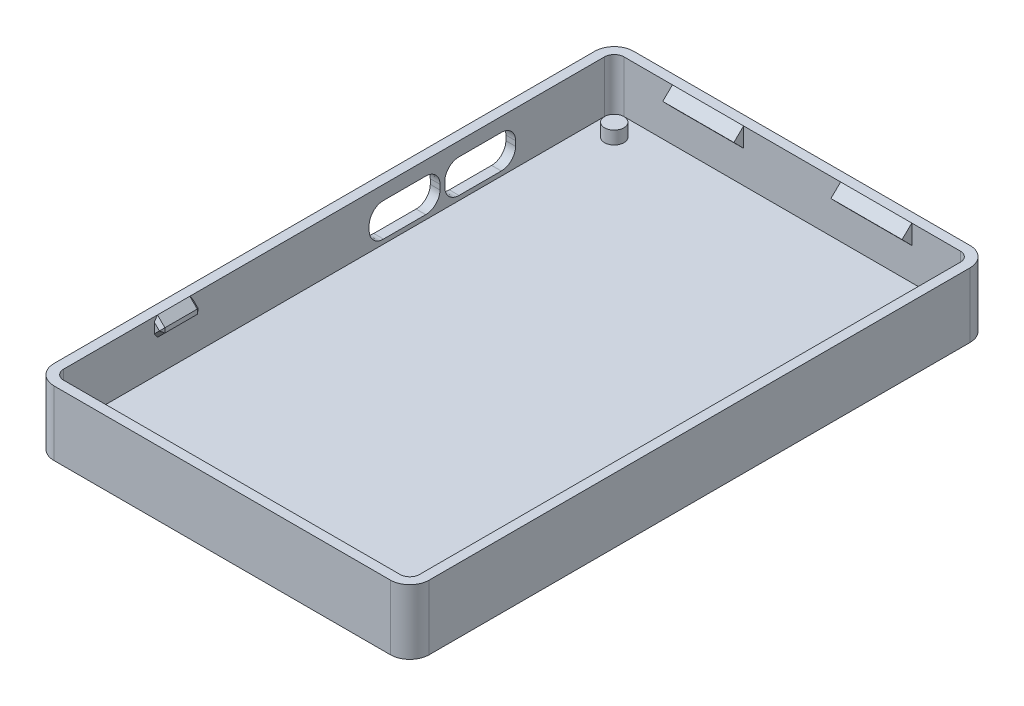
SolidWorks part; units mm, degrees
ref_plane "前视基准面" through (0, 0, 0) normal (0, 0, 1) x (1, 0, 0)
ref_plane "上视基准面" through (0, 0, 0) normal (0, 1, 0) x (1, 0, 0)
ref_plane "右视基准面" through (0, 0, 0) normal (1, 0, 0) x (0, 0, -1)
other "Configuration Table"
sketch "草图1" plane through (0, 0, 0) normal (0, 1, 0) x (1, 0, 0)
  line L1 (3, 0) -> (55, 0)
  line L2 (0, 3) -> (0, 86.6)
  line L3 (3, 89.6) -> (55, 89.6)
  line L4 (58, 3) -> (58, 86.6)
  arc A0 (58, 86.6) -> (55, 89.6) centre (55, 86.6) ccw
  arc A1 (55, 0) -> (58, 3) centre (55, 3) ccw
  arc A2 (3, 0) -> (0, 3) centre (3, 3) cw
  arc A3 (0, 86.6) -> (3, 89.6) centre (3, 86.6) cw
  point P7 (58, 89.6)
  point P10 (58, 0)
  point P13 (0, 0)
  point P16 (0, 89.6)
  dimension "D3" = 3
  dimension "D1" = 89.6
  dimension "D2" = 58
extrude "凸台-拉伸1" add sketch "草图1" along normal blind 2
sketch "草图3" plane through (0, 2, 0) normal (0, 1, 0) x (1, 0, 0)
  line L0 (0, 86.6) -> (0, 3) construction
  line L1 (3, 0) -> (55, 0) construction
  line L2 (58, 3) -> (58, 86.6) construction
  line L3 (55, 89.6) -> (3, 89.6) construction
  line L4 (0, 86.6) -> (0, 3)
  line L5 (3, 0) -> (55, 0)
  line L6 (58, 3) -> (58, 86.6)
  line L7 (55, 89.6) -> (3, 89.6)
  line L8 (1.5, 86.6) -> (1.5, 3)
  line L9 (3, 1.5) -> (55, 1.5)
  line L10 (56.5, 3) -> (56.5, 86.6)
  line L11 (55, 88.1) -> (3, 88.1)
  arc A0 (0, 3) -> (3, 0) centre (3, 3) ccw construction
  arc A1 (55, 0) -> (58, 3) centre (55, 3) ccw construction
  arc A2 (58, 86.6) -> (55, 89.6) centre (55, 86.6) ccw construction
  arc A3 (3, 89.6) -> (0, 86.6) centre (3, 86.6) ccw construction
  arc A4 (0, 3) -> (3, 0) centre (3, 3) ccw
  arc A5 (55, 0) -> (58, 3) centre (55, 3) ccw
  arc A6 (58, 86.6) -> (55, 89.6) centre (55, 86.6) ccw
  arc A7 (3, 89.6) -> (0, 86.6) centre (3, 86.6) ccw
  arc A8 (1.5, 3) -> (3, 1.5) centre (3, 3) ccw
  arc A9 (55, 1.5) -> (56.5, 3) centre (55, 3) ccw
  arc A10 (56.5, 86.6) -> (55, 88.1) centre (55, 86.6) ccw
  arc A11 (3, 88.1) -> (1.5, 86.6) centre (3, 86.6) ccw
  dimension "D1" = 1.5
extrude "凸台-拉伸2" add sketch "草图3" along normal blind 11
sketch "草图5" plane through (0, 2, 0) normal (0, 1, 0) x (1, 0, 0)
  line L0 (55, 88.1) -> (3, 88.1) construction
  line L1 (1.5, 86.6) -> (1.5, 3) construction
  line L2 (29, 89.6) -> (29, 0) construction
  line L3 (55, 89.6) -> (3, 89.6) construction
  line L4 (3, 0) -> (55, 0) construction
  line L5 (0, 44.8) -> (58, 44.8) construction
  line L6 (0, 86.6) -> (0, 3) construction
  line L7 (58, 3) -> (58, 86.6) construction
  circle A0 centre (5, 84.6) radius 1.5
  circle A1 centre (53, 84.6) radius 1.5
  circle A2 centre (53, 5) radius 1.5
  circle A3 centre (5, 5) radius 1.5
  dimension "D3" = 3
  dimension "D1" = 3.5
  dimension "D2" = 3.5
extrude "凸台-拉伸3" add sketch "草图5" along normal blind 2
extrude "切除-拉伸1" cut sketch "草图6" against normal blind 2 contours S23 L27 S22 L26 S21 L25 S20 L24 L6 S7 L7 S5 L4 S4 L5 S6 | S7 L6 S6 L5 S4 L4 S5 L7 | S31 L31 S30 L30 S29 L29 S28 L28 L23 S15 L20 S12 L21 S13 L22 S14 | S15 L23 S14 L22 S13 L21 S12 L20 region at (0, 5.27, -67.3785) region at (0, 5.27, -55.6945) region at (0, 7.7291, -67.3785) region at (0, 7.7291, -55.6945)
sketch "草图6" plane through (0, 2, -82.9995) normal (-1, 0, 0) x (0, 1, 0)
  line L4 (3.65, -20.091) -> (2.89, -20.091)
  line L5 (1.69, -18.891) -> (1.69, -12.351)
  line L6 (2.89, -11.151) -> (3.65, -11.151)
  line L7 (4.85, -12.351) -> (4.85, -18.891)
  line L16 (-2, 3.6005) -> (-2, -79.9995)
  line L17 (-2, -79.9995) -> (8, -79.9995)
  line L19 (8, 3.6005) -> (-2, 3.6005)
  line L20 (4.85, -24.0351) -> (4.85, -30.5751)
  line L21 (3.65, -31.7751) -> (2.89, -31.7751)
  line L22 (1.69, -30.5751) -> (1.69, -24.0351)
  line L23 (2.89, -22.8351) -> (3.65, -22.8351)
  line L24 (5.85, -12.351) -> (5.85, -18.891)
  line L25 (3.65, -21.091) -> (2.89, -21.091)
  line L26 (0.69, -18.891) -> (0.69, -12.351)
  line L27 (2.89, -10.151) -> (3.65, -10.151)
  line L28 (5.85, -24.0351) -> (5.85, -30.5751)
  line L29 (3.65, -32.7751) -> (2.89, -32.7751)
  line L30 (0.69, -30.5751) -> (0.69, -24.0351)
  line L31 (2.89, -21.8351) -> (3.65, -21.8351)
  line L36 (8, -79.9995) -> (8, 3.6005)
  spline S4 degree 3 poles (2.89, -20.091) (2.1871, -20.091) (1.69, -19.594) (1.69, -18.891) knots 0 0 0 0 1 1 1 1 weights 1 0.804738 0.804738 1
  spline S5 degree 3 poles (4.85, -18.891) (4.85, -19.594) (4.353, -20.091) (3.65, -20.091) knots 0 0 0 0 1 1 1 1 weights 1 0.804738 0.804738 1
  spline S6 degree 3 poles (1.69, -12.351) (1.69, -11.6481) (2.1871, -11.151) (2.89, -11.151) knots 0 0 0 0 1 1 1 1 weights 1 0.804738 0.804738 1
  spline S7 degree 3 poles (3.65, -11.151) (4.353, -11.151) (4.85, -11.6481) (4.85, -12.351) knots 0 0 0 0 1 1 1 1 weights 1 0.804738 0.804738 1
  spline S12 degree 3 poles (4.85, -30.5751) (4.85, -31.278) (4.353, -31.7751) (3.65, -31.7751) knots 0 0 0 0 1 1 1 1 weights 1 0.804738 0.804738 1
  spline S13 degree 3 poles (2.89, -31.7751) (2.1871, -31.7751) (1.69, -31.278) (1.69, -30.5751) knots 0 0 0 0 1 1 1 1 weights 1 0.804738 0.804738 1
  spline S14 degree 3 poles (1.69, -24.0351) (1.69, -23.3321) (2.1871, -22.8351) (2.89, -22.8351) knots 0 0 0 0 1 1 1 1 weights 1 0.804738 0.804738 1
  spline S15 degree 3 poles (3.65, -22.8351) (4.353, -22.8351) (4.85, -23.3321) (4.85, -24.0351) knots 0 0 0 0 1 1 1 1 weights 1 0.804738 0.804738 1
  spline S20 degree 3 poles (5.85, -18.891) (5.85, -19.1658) (5.7555, -19.7032) (5.2541, -20.4951) (4.4622, -20.9965) (3.9248, -21.091) (3.65, -21.091) knots 0 0 0 0 0.25 0.5 0.75 1 1 1 1
  spline S21 degree 3 poles (2.89, -21.091) (2.6152, -21.091) (2.0779, -20.9965) (1.286, -20.4951) (0.7845, -19.7032) (0.69, -19.1658) (0.69, -18.891) knots 0 0 0 0 0.25 0.5 0.75 1 1 1 1
  spline S22 degree 3 poles (0.69, -12.351) (0.69, -12.0762) (0.7845, -11.5389) (1.286, -10.747) (2.0779, -10.2456) (2.6152, -10.151) (2.89, -10.151) knots 0 0 0 0 0.25 0.5 0.75 1 1 1 1
  spline S23 degree 3 poles (3.65, -10.151) (3.9248, -10.151) (4.4622, -10.2456) (5.2541, -10.747) (5.7555, -11.5389) (5.85, -12.0762) (5.85, -12.351) knots 0 0 0 0 0.25 0.5 0.75 1 1 1 1
  spline S28 degree 3 poles (5.85, -30.5751) (5.85, -30.8499) (5.7555, -31.3872) (5.2541, -32.1791) (4.4622, -32.6805) (3.9248, -32.7751) (3.65, -32.7751) knots 0 0 0 0 0.25 0.5 0.75 1 1 1 1
  spline S29 degree 3 poles (2.89, -32.7751) (2.6152, -32.7751) (2.0779, -32.6805) (1.286, -32.1791) (0.7845, -31.3872) (0.69, -30.8499) (0.69, -30.5751) knots 0 0 0 0 0.25 0.5 0.75 1 1 1 1
  spline S30 degree 3 poles (0.69, -24.0351) (0.69, -23.7603) (0.7845, -23.2229) (1.286, -22.431) (2.0779, -21.9296) (2.6152, -21.8351) (2.89, -21.8351) knots 0 0 0 0 0.25 0.5 0.75 1 1 1 1
  spline S31 degree 3 poles (3.65, -21.8351) (3.9248, -21.8351) (4.4622, -21.9296) (5.2541, -22.431) (5.7555, -23.2229) (5.85, -23.7603) (5.85, -24.0351) knots 0 0 0 0 0.25 0.5 0.75 1 1 1 1
sketch "草图7" plane through (0, 13, 0) normal (0, 1, 0) x (1, 0, 0)
  line L0 (3, 1.5) -> (55, 1.5) construction
  line L1 (1.5, 86.6) -> (1.5, 3) construction
  line L2 (55, 88.1) -> (3, 88.1) construction
  line L3 (56.5, 3) -> (56.5, 86.6) construction
  line L4 (0, 86.6) -> (0, 3)
  line L5 (3, 0) -> (55, 0)
  line L6 (58, 3) -> (58, 86.6)
  line L7 (55, 89.6) -> (3, 89.6)
  line L8 (0, 86.6) -> (0, 3)
  line L9 (3, 0) -> (55, 0)
  line L10 (58, 3) -> (58, 86.6)
  line L11 (55, 89.6) -> (3, 89.6)
  line L12 (3, 1.5) -> (55, 1.5)
  line L13 (1.5, 86.6) -> (1.5, 3)
  line L14 (55, 88.1) -> (3, 88.1)
  line L15 (56.5, 3) -> (56.5, 86.6)
  arc A0 (55, 1.5) -> (56.5, 3) centre (55, 3) ccw construction
  arc A1 (1.5, 3) -> (3, 1.5) centre (3, 3) ccw construction
  arc A2 (3, 88.1) -> (1.5, 86.6) centre (3, 86.6) ccw construction
  arc A3 (56.5, 86.6) -> (55, 88.1) centre (55, 86.6) ccw construction
  arc A4 (3, 89.6) -> (0, 86.6) centre (3, 86.6) ccw
  arc A5 (0, 3) -> (3, 0) centre (3, 3) ccw
  arc A6 (55, 0) -> (58, 3) centre (55, 3) ccw
  arc A7 (58, 86.6) -> (55, 89.6) centre (55, 86.6) ccw
  arc A8 (3, 89.6) -> (0, 86.6) centre (3, 86.6) ccw
  arc A9 (0, 3) -> (3, 0) centre (3, 3) ccw
  arc A10 (55, 0) -> (58, 3) centre (55, 3) ccw
  arc A11 (58, 86.6) -> (55, 89.6) centre (55, 86.6) ccw
  arc A12 (55, 1.5) -> (56.5, 3) centre (55, 3) ccw
  arc A13 (1.5, 3) -> (3, 1.5) centre (3, 3) ccw
  arc A14 (3, 88.1) -> (1.5, 86.6) centre (3, 86.6) ccw
  arc A15 (56.5, 86.6) -> (55, 88.1) centre (55, 86.6) ccw
  dimension "D1" = 0
extrude "切除-拉伸2" cut sketch "草图7" against normal blind 3
sketch3d "3D草图3"
  line L0 (55, 2, -88.1) -> (3, 2, -88.1) construction
  line L1 (56.5, 2, -3) -> (56.5, 2, -86.6) construction
  line L4 (1.5, 2, -86.6) -> (1.5, 2, -3) construction
  point P0 (40, 2, -88.1)
  dimension "D1" = 16.5
  dimension "D2" = 55
sketch "草图8" plane through (0, 0, -88.1) normal (0, 0, 1) x (1, 0, 0)
  line L0 (29, 2) -> (29, 10) construction
  line L1 (10.5, 10) -> (21.5, 10)
  line L2 (10.5, 10) -> (10.5, 7)
  line L3 (10.5, 7) -> (21.5, 7)
  line L4 (55, 2) -> (55, 10)
  line L5 (55, 10) -> (3, 10)
  line L6 (3, 10) -> (3, 2)
  line L7 (3, 2) -> (55, 2)
  line L8 (55, 2) -> (55, 10)
  line L9 (55, 10) -> (3, 10)
  line L10 (3, 10) -> (3, 2)
  line L11 (3, 2) -> (55, 2)
  line L12 (21.5, 10) -> (21.5, 7)
  line L13 (47.5, 7) -> (36.5, 7)
  line L14 (36.5, 10) -> (36.5, 7)
  line L15 (47.5, 10) -> (36.5, 10)
  line L16 (47.5, 10) -> (47.5, 7)
  line M10 (55, 10) -> (3, 10)
  dimension "D2" = 11
  dimension "D3" = 3
  dimension "D4" = 7.5
  dimension "D1" = 0
extrude "凸台-拉伸4" add sketch "草图8" along normal blind 1.5 contours L12 L2 L3 M10 | L16 L9 L14 L13 region at (16, 8.5, -88.1) region at (42, 8.5, -88.1)
sketch "草图10" plane through (10.5, 0, 0) normal (-1, 0, 0) x (0, 0, 1)
  line L0 (-88.1, 8.5343) -> (-86.6, 8.5343) construction
  line L1 (-88.1, 10) -> (-86.6, 8.5343)
  line L2 (-86.6, 8.5343) -> (-88.1, 7)
  line L4 (-88.1, 10) -> (-88.1, 7)
  line L5 (-88.1, 7) -> (-86.6, 7)
  line L6 (-86.6, 7) -> (-86.6, 10)
  line L7 (-86.6, 10) -> (-88.1, 10)
  line L8 (-88.1, 10) -> (-88.1, 7)
  line L9 (-88.1, 7) -> (-86.6, 7)
  line L10 (-86.6, 7) -> (-86.6, 10)
  line L11 (-86.6, 10) -> (-88.1, 10)
  line M6 (-88.1, 7) -> (-86.6, 7)
  line M7 (-86.6, 7) -> (-86.6, 10)
  line M8 (-86.6, 10) -> (-88.1, 10)
  dimension "D1" = 0
extrude "切除-拉伸3" cut sketch "草图10" against normal blind 40 contours L1 M8 M7 | L2 M7 M6 region at (10.5, 9.5114, -87.1) region at (10.5, 7.5114, -87.1)
sketch "草图11" plane through (1.5, 0, 0) normal (1, 0, 0) x (0, 0, -1)
  line L1 (17, 10) -> (23, 10)
  line L2 (17, 10) -> (17, 7)
  line L3 (17, 7) -> (23, 7)
  line L4 (86.6, 2) -> (86.6, 10)
  line L5 (86.6, 10) -> (3, 10)
  line L6 (3, 10) -> (3, 2)
  line L7 (3, 2) -> (86.6, 2)
  line L8 (86.6, 2) -> (86.6, 10)
  line L9 (86.6, 10) -> (3, 10)
  line L10 (3, 10) -> (3, 2)
  line L11 (3, 2) -> (86.6, 2)
  line L12 (23, 10) -> (23, 7)
  dimension "D2" = 14
  dimension "D3" = 6
  dimension "D4" = 3
  dimension "D1" = 0
extrude "凸台-拉伸5" add sketch "草图11" along normal blind 1.5 contours L1 L12 L3 L2
sketch "草图12" plane through (0, 0, -17) normal (0, 0, 1) x (1, 0, 0)
  line L0 (3, 8.5) -> (1.5, 8.5) construction
  line L1 (3, 8.5) -> (1.5, 10)
  line L2 (1.5, 7) -> (3, 8.5)
  line L4 (1.5, 10) -> (1.5, 7)
  line L5 (1.5, 7) -> (3, 7)
  line L6 (3, 7) -> (3, 10)
  line L7 (3, 10) -> (1.5, 10)
  line L8 (1.5, 10) -> (1.5, 7)
  line L9 (1.5, 7) -> (3, 7)
  line L10 (3, 7) -> (3, 10)
  line L11 (3, 10) -> (1.5, 10)
  line M6 (1.5, 7) -> (3, 7)
  line M7 (3, 7) -> (3, 10)
  line M8 (3, 10) -> (1.5, 10)
  dimension "D1" = 0
extrude "切除-拉伸4" cut sketch "草图12" against normal blind 7 contours L1 M7 M8 | L2 M6 M7 region at (2.5, 7.5, -17) region at (2.5, 9.5, -17)
sketch "草图13" plane through (56.5, 0, 0) normal (-1, 0, 0) x (0, 0, 1)
  line L1 (-23, 10) -> (-17, 10)
  line L2 (-23, 10) -> (-23, 7)
  line L3 (-23, 7) -> (-17, 7)
  line L4 (-3, 2) -> (-3, 10)
  line L5 (-3, 10) -> (-86.6, 10)
  line L6 (-86.6, 10) -> (-86.6, 2)
  line L7 (-86.6, 2) -> (-3, 2)
  line L8 (-3, 2) -> (-3, 10)
  line L9 (-3, 10) -> (-86.6, 10)
  line L10 (-86.6, 10) -> (-86.6, 2)
  line L11 (-86.6, 2) -> (-3, 2)
  line L12 (-17, 10) -> (-17, 7)
  line M6 (-3, 10) -> (-86.6, 10)
  dimension "D2" = 14
  dimension "D3" = 6
  dimension "D4" = 3
  dimension "D1" = 0
extrude "凸台-拉伸6" add sketch "草图13" along normal blind 1.5 contours L12 L2 L3 M6 region at (56.5, 8.5, -20)
sketch "草图15" plane through (0, 0, -23) normal (0, 0, -1) x (-1, 0, 0)
  line L0 (-56.5, 10) -> (-55, 8.5)
  line L1 (-55, 8.5) -> (-56.5, 7)
  line L4 (-56.5, 10) -> (-56.5, 7)
  line L5 (-56.5, 7) -> (-55, 7)
  line L6 (-55, 7) -> (-55, 10)
  line L7 (-55, 10) -> (-56.5, 10)
  line L8 (-56.5, 10) -> (-56.5, 7)
  line L9 (-56.5, 7) -> (-55, 7)
  line L10 (-55, 7) -> (-55, 10)
  line L11 (-55, 10) -> (-56.5, 10)
  line M6 (-56.5, 7) -> (-55, 7)
  line M7 (-55, 7) -> (-55, 10)
  line M8 (-55, 10) -> (-56.5, 10)
  dimension "D1" = 0
extrude "切除-拉伸5" cut sketch "草图15" against normal blind 7 contours L0 M8 M7 | L1 M7 M6 region at (55.5, 9.5, -23) region at (55.5, 7.5, -23)
chamfer "倒角1" distance 0.5 angle 45 5 edges at (2.25, 7.75, -17) (2.25, 7.75, -23) (2.25, 9.25, -23) (3, 8.5, -20) (2.25, 9.25, -17)
chamfer "倒角2" distance 0.5 angle 45 5 edges at (55.75, 7.75, -23) (55.75, 7.75, -17) (55.75, 9.25, -17) (55.75, 9.25, -23) (55, 8.5, -20)
